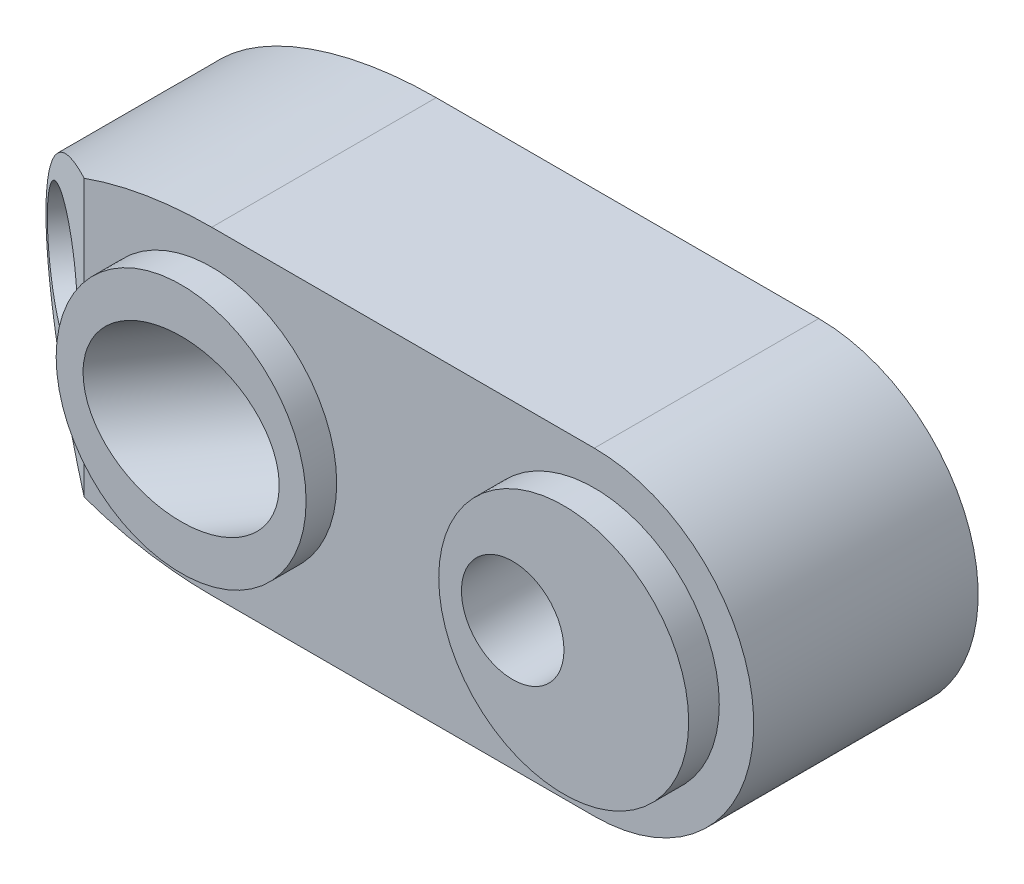
SolidWorks part; units mm, degrees
ref_plane "Front" through (0, 0, 0) normal (0, 0, 1) x (1, 0, 0)
ref_plane "Top" through (0, 0, 0) normal (0, 1, 0) x (1, 0, 0)
ref_plane "Right" through (0, 0, 0) normal (1, 0, 0) x (0, 0, -1)
sketch "Sketch1" plane through (0, 0, 0) normal (0, 0, 1) x (1, 0, 0)
  line L0 (0, 7.9375) -> (19.05, 7.9375)
  line L1 (0, -7.9375) -> (19.05, -7.9375)
  line L2 (0, 0) -> (0, -3.5453) construction
  arc A0 (0, 7.9375) -> (0, -7.9375) centre (0, 0) ccw construction
  arc A1 (19.05, -7.9375) -> (19.05, 7.9375) centre (19.05, 0) ccw
  ellipse E0 centre (0, 0) end of major axis (-12.7, 0) minor radius 7.9375 (0, 7.9375) -> (0, -7.9375) ccw
  dimension "D1" = 19.05
  dimension "D2" = 15.875
  dimension "D3" = 12.7
extrude "Boss-Extrude1" add sketch "Sketch1" against normal blind 12.7
sketch "Sketch2" plane through (0, 0, 0) normal (0, 0, 1) x (1, 0, 0)
  circle A2 centre (0, 0) radius 6.223
  circle A3 centre (19.05, 0) radius 6.223
  dimension "D1" = 12.446
extrude "Cut-Extrude1" cut sketch "Sketch2" against normal blind 1.524 flip side to cut
ref_plane "Plane1" through (0, 0, 0) normal (-0.5736, 0, 0.8192) x (0, -1, 0)
sketch "Sketch3" plane through (0, 0, 0) normal (-0.5736, 0, 0.8192) x (0, -1, 0)
  line L0 (0, 0) -> (0, -10.5) construction
  circle A0 centre (0, 0) radius 4
  dimension "D1" = 8
  dimension "D2" = 10.5
extrude "Cut-Extrude2" cut sketch "Sketch3" against normal through all both and the other way through all
ref_plane "Plane2" through (3.6422, 0, -5.2016) normal (-0.5736, 0, 0.8192) x (0, -1, 0)
sketch "Sketch5" plane through (3.6422, 0, -5.2016) normal (-0.5736, 0, 0.8192) x (0, -1, 0)
  line L0 (5.5, 5.5) -> (0, 0) construction
  line L1 (5.5, 5.5) -> (-5.5, 5.5)
  line L2 (5.5, 5.5) -> (5.5, -15.5)
  line L3 (5.5, -15.5) -> (-5.5, -15.5)
  line L4 (-5.5, 5.5) -> (-5.5, -15.5)
  line L5 (0, 0) -> (-5.5, 5.5) construction
  dimension "D1" = 11
  dimension "D2" = 21
extrude "Cut-Extrude3" cut sketch "Sketch5" against normal through all
sketch "Sketch8" plane through (0, 0, 0) normal (0, 1, 0) x (1, 0, 0)
  line L0 (-12.7, 5.9703) -> (-6.35, 1.524)
  line L1 (-12.7, 5.9703) -> (-14.7891, 2.9868)
  line L2 (-6.35, 1.524) -> (-8.4391, -1.4595)
  line L3 (-14.7891, 2.9868) -> (-8.4391, -1.4595)
  line L9 (-12.7, 1.524) -> (0, 1.524) construction
  line L10 (-12.7, 12.7) -> (-12.7, 1.524) construction
  line L11 (2.0449, 6.32) -> (5.2395, 4.0832) construction
  line L12 (-12.7, 12.7) -> (-12.7, 1.524) construction
  point P7 (-14.1223, 8.4001)
  dimension "D1" = 6.35
extrude "Cut-Extrude4" cut sketch "Sketch8" against normal through all both and the other way through all
sketch "Sketch4" plane through (0, 0, 0) normal (0, 1, 0) x (1, 0, 0)
  line L0 (-3.1604, 13.7927) -> (-9.9742, 4.0616)
  line L1 (-9.9742, 4.0616) -> (-12.4709, 5.8099)
  line L2 (-12.4709, 5.8099) -> (-10.3694, 8.8111)
  line L3 (-10.3694, 8.8111) -> (-9.4331, 8.1555)
  line L4 (-9.4331, 8.1555) -> (-4.7209, 14.8853)
  line L5 (-4.7209, 14.8853) -> (-3.1604, 13.7927)
  line L6 (-3.1604, 13.7927) -> (-1.5999, 12.7) construction
  line L8 (0, 0) -> (-8.6011, 6.0226) construction
  line L9 (-9.9742, 4.0616) -> (-13.9328, -1.5919) construction
  line L10 (-7.0666, 12.7) -> (8.1475, 2.0469) construction
  line L11 (19.05, 12.7) -> (0, 12.7) construction
  dimension "D1" = 3.81
  dimension "D2" = 5.08
  dimension "D3" = 6.096
revolve "Cut-Revolve1" cut sketch "Sketch4" angle 360 about L9
hole_wizard "1/4-20 Tapped Hole1" positions "Sketch6" profile "Sketch7" tap size "1/4-20" standard "ANSI Inch" end condition through all
sketch "Sketch6" plane through (0, 0, 0) normal (0, 0, 1) x (1, 0, 0)
  circle A0 centre (19.05, 0) radius 6.223 construction
  point P0 (16.51, 0)
  dimension "D1" = 2.54
sketch "Sketch7" plane through (16.51, 0, 0) normal (1, 0, 0) x (0, -1, 0)
  line L0 (0, 0) -> (0, 12.7)
  line L1 (0, 12.7) -> (2.5527, 12.7)
  line L2 (2.5527, 12.7) -> (2.5527, 0)
  line L5 (2.5527, 0) -> (0, 0)
  line L11 (0, -6.35) -> (0, 107.95) construction
  dimension "Thru Tap Drill Dia." = 5.1054
  dimension "Thru Tap Drill Depth" = 12.7
cosmetic thread "Hole Thread1" parameters "D2"=6.35
